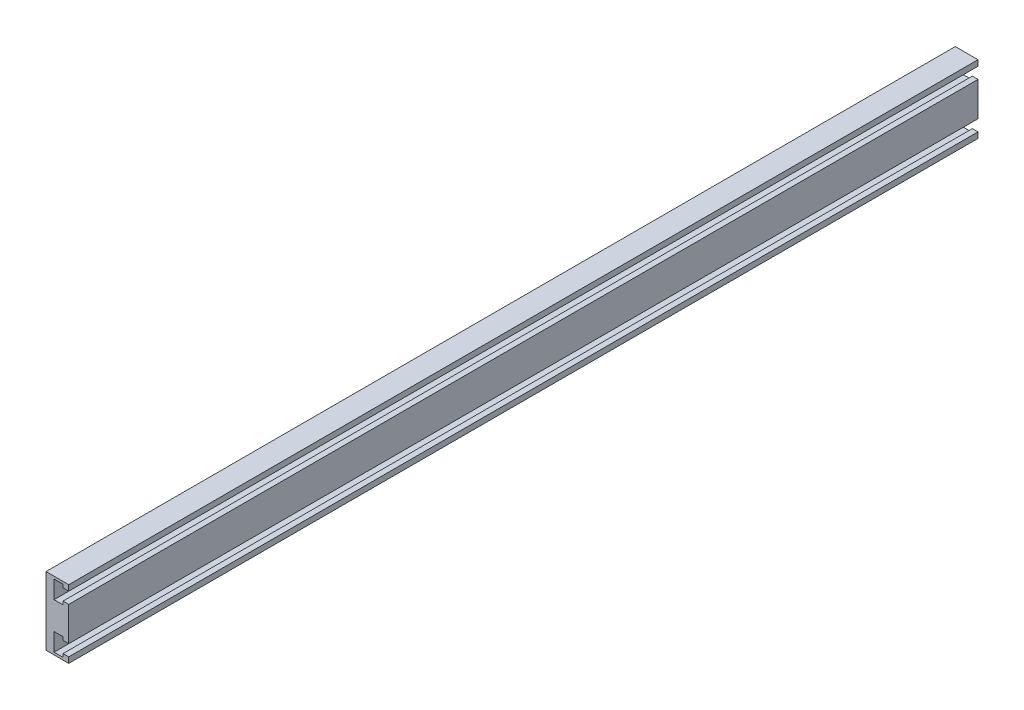
SolidWorks part; units mm, degrees
ref_plane "Front Plane" through (0, 0, 0) normal (0, 0, 1) x (1, 0, 0)
ref_plane "Top Plane" through (0, 0, 0) normal (0, 1, 0) x (1, 0, 0)
ref_plane "Right Plane" through (0, 0, 0) normal (1, 0, 0) x (0, 0, -1)
sketch "Sketch1" plane through (0, 0, 0) normal (0, 0, 1) x (1, 0, 0)
  line L0 (6.35, -19.05) -> (6.35, -15.875)
  line L1 (-6.35, -19.05) -> (6.35, -19.05)
  line L2 (-6.35, -19.05) -> (-6.35, 19.05)
  line L3 (-6.35, 19.05) -> (6.35, 19.05)
  line L5 (6.35, 15.875) -> (3.175, 15.875)
  line L6 (3.175, 15.875) -> (3.175, 17.7)
  line L14 (6.35, 15.875) -> (6.35, 19.05)
  line L15 (6.35, -9.525) -> (3.175, -9.525)
  line L16 (6.35, -15.875) -> (3.175, -15.875)
  line L17 (3.175, -15.875) -> (3.175, -17.7)
  line L18 (3.175, -17.7) -> (-1.825, -17.7)
  line L19 (-1.825, -17.7) -> (-1.825, -7.7)
  line L20 (-1.825, -7.7) -> (3.175, -7.7)
  line L21 (3.175, -7.7) -> (3.175, -9.525)
  line L22 (3.175, 17.7) -> (-1.825, 17.7)
  line L23 (-1.825, 17.7) -> (-1.825, 7.7)
  line L24 (-1.825, 7.7) -> (3.175, 7.7)
  line L25 (3.175, 7.7) -> (3.175, 9.525)
  line L26 (3.175, 9.525) -> (6.35, 9.525)
  line L27 (6.35, 9.525) -> (6.35, -9.525)
  line L28 (3.175, 17.7) -> (3.175, 7.7) construction
  line L29 (6.35, 15.875) -> (6.35, 9.525) construction
  line L30 (3.175, -7.7) -> (3.175, -17.7) construction
  line L31 (6.35, -9.525) -> (6.35, -15.875) construction
  point P0 (0, 0)
  point P12 (3.175, 12.7)
  point P23 (6.35, 12.7)
  point P24 (3.175, -12.7)
  point P25 (6.35, -12.7)
  dimension "D1" = 38.1
  dimension "D2" = 12.7
  dimension "D3" = 3.175
  dimension "D4" = 6.35
  dimension "D5" = 6.35
  dimension "D6" = 3.175
  dimension "D7" = 5
  dimension "D8" = 3.175
  dimension "D9" = 0
  dimension "D10" = 0
  dimension "D11" = 5
  dimension "D12" = 12.7
  dimension "D13" = 10
  dimension "D14" = 0
  dimension "D15" = 5
  dimension "D16" = 5
  dimension "D17" = 10
  dimension "D18" = 0
extrude "Boss-Extrude1" add sketch "Sketch1" along normal blind 254 and the other way blind 254 contours L2 L3 L14 L5 L6 L22 L23 L24 L25 L26 L27 L15 L21 L20 L19 L18 L17 L16 L0 L1
